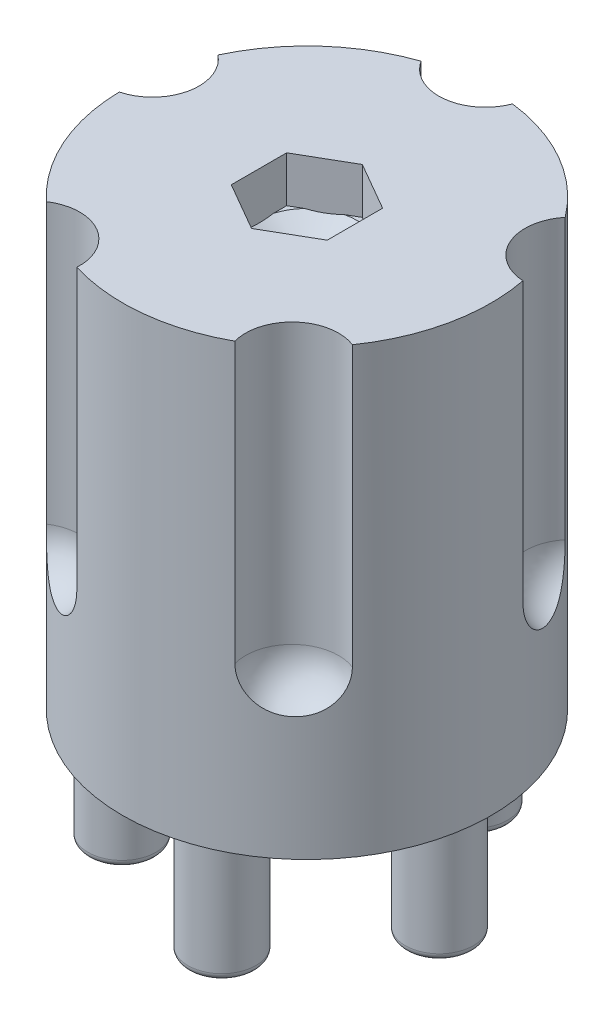
SolidWorks part; units mm, degrees
ref_plane "Front Plane" through (0, 0, 0) normal (0, 0, 1) x (1, 0, 0)
ref_plane "Top Plane" through (0, 0, 0) normal (0, 1, 0) x (1, 0, 0)
ref_plane "Right Plane" through (0, 0, 0) normal (1, 0, 0) x (0, 0, -1)
sketch "Sketch1" plane through (0, 0, 0) normal (0, 1, 0) x (1, 0, 0)
  circle A0 centre (0, 0) radius 25.75
  dimension "D1" = 51.5
extrude "Boss-Extrude1" add sketch "Sketch1" along normal blind 62
sketch "Sketch2" plane through (0, 0, 0) normal (0, -1, 0) x (1, 0, 0)
  circle A0 centre (0, 0) radius 18.5 construction
  circle A1 centre (18.5, 0) radius 4.75
  circle A2 centre (5.7168, -17.5945) radius 4.75
  circle A3 centre (-14.9668, -10.874) radius 4.75
  circle A4 centre (-14.9668, 10.874) radius 4.75
  circle A5 centre (5.7168, 17.5945) radius 4.75
  point P16 (0, 0)
  dimension "D2" = 9.5
  dimension "D3" = 37
  dimension "D1" = 5
extrude "Boss-Extrude2" add sketch "Sketch2" along normal blind 18
fillet "Fillet1" radius 1 5 edges at (5.7168, 0, 22.3445) (-14.9668, 0, 15.624) (-14.9668, 0, -6.124) (5.7168, 0, -12.8445) (18.5, 0, 4.75)
fillet "Fillet2" radius 1 5 edges at (-14.9668, -18, -15.624) (-14.9668, -18, 6.124) (5.7168, -18, 12.8445) (18.5, -18, -4.75) (5.7168, -18, -22.3445)
sketch "Sketch3" plane through (0, 62, 0) normal (0, 1, 0) x (1, 0, 0)
  line L1 (0, -7.7365) -> (6.7, -3.8682)
  line L2 (6.7, -3.8682) -> (6.7, 3.8682)
  line L3 (6.7, 3.8682) -> (0, 7.7365)
  line L4 (0, 7.7365) -> (-6.7, 3.8682)
  line L5 (-6.7, 3.8682) -> (-6.7, -3.8682)
  line L6 (-6.7, -3.8682) -> (0, -7.7365)
  circle A0 centre (0, 0) radius 6.7 construction
  dimension "D1" = 13.4
extrude "Cut-Extrude1" cut sketch "Sketch3" against normal blind 6.4
sketch "Sketch4" plane through (0, 0, 0) normal (0, -1, 0) x (1, 0, 0)
  circle A0 centre (0, 0) radius 10
  dimension "D1" = 20
extrude "Cut-Extrude2" cut sketch "Sketch4" against normal blind 45
sketch "Sketch5" plane through (0, 45, 0) normal (0, -1, 0) x (1, 0, 0)
  circle A0 centre (0, 0) radius 4
  dimension "D1" = 8
extrude "Cut-Extrude3" cut sketch "Sketch5" against normal through all
sketch "Sketch6" plane through (0, 62, 0) normal (0, 1, 0) x (1, 0, 0)
  line L0 (-3.35, -5.8024) -> (-14, -24.2487) construction
  line L1 (-6.7, -3.8682) -> (0, -7.7365) construction
  circle A0 centre (0, 0) radius 28 construction
  circle A1 centre (-14, -24.2487) radius 6.5
  circle A2 centre (-27.3881, 5.8215) radius 6.5
  circle A3 centre (-2.9268, 27.8466) radius 6.5
  circle A4 centre (25.5793, 11.3886) radius 6.5
  circle A5 centre (18.7357, -20.8081) radius 6.5
  point P16 (0, 0)
  dimension "D2" = 13
  dimension "D3" = 56
  dimension "D1" = 5
extrude "Cut-Extrude4" cut sketch "Sketch6" against normal blind 45
fillet "Fillet3" radius 6 5 edges at (-10.75, 17, 18.6195) (-21.0302, 17, -4.4701) (-2.2474, 17, -21.3822) (19.6412, 17, -8.7448) (14.3863, 17, 15.9776)
chamfer "Chamfer3" distance 3 angle 30 1 edges at (0, 55.6, 4) first distance on face at (0, 55.6, 4)
sketch "Sketch7" plane through (0, 45, 0) normal (0, -1, 0) x (1, 0, 0)
  circle A0 centre (0, 0) radius 6.6
  dimension "D1" = 13.2
extrude "Cut-Extrude5" cut sketch "Sketch7" against normal blind 6
